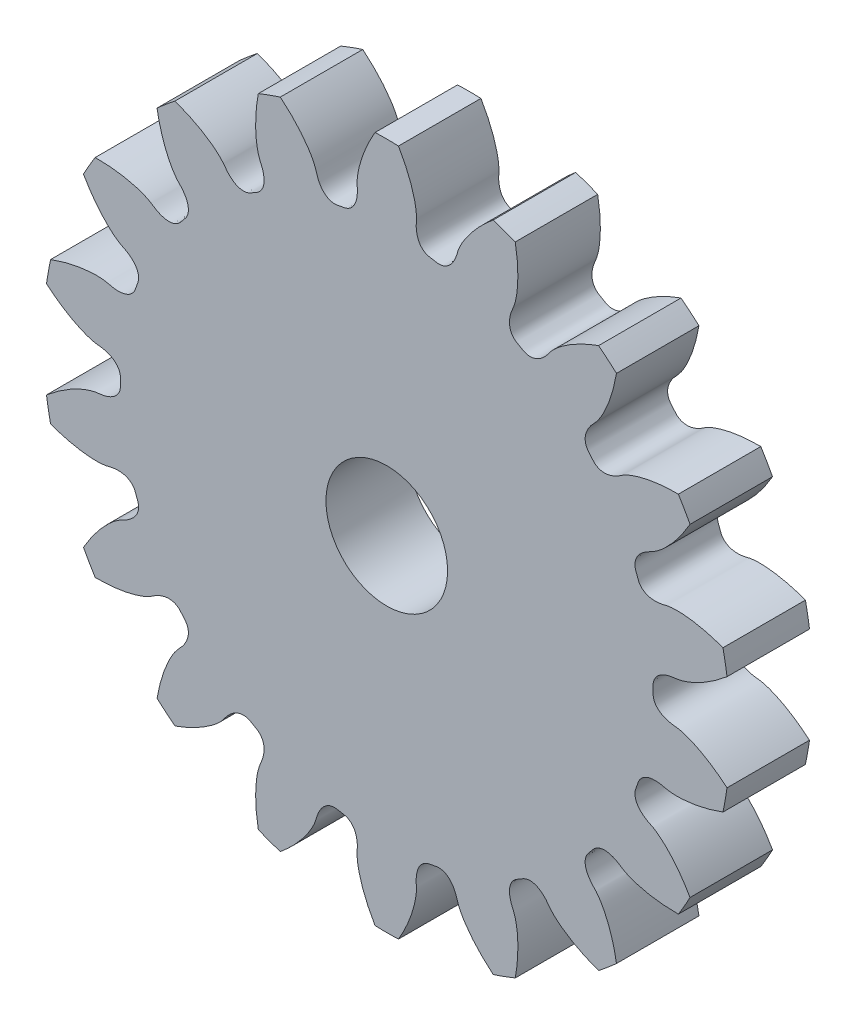
SolidWorks part; units mm, degrees
ref_plane "Front Plane" through (0, 0, 0) normal (0, 0, 1) x (1, 0, 0)
ref_plane "Top Plane" through (0, 0, 0) normal (0, 1, 0) x (1, 0, 0)
ref_plane "Right Plane" through (0, 0, 0) normal (1, 0, 0) x (0, 0, -1)
ref_axis "Axis1" through (0, 0, 55) along (0, 0, -1)
sketch "SketchRevolveSpurGear1" plane through (0, 0, 0) normal (1, 0, 0) x (0, 0, -1)
  line L0 (0, 0) -> (1, 0) construction
  line L1 (-2, 0) -> (-2, 16.6667)
  line L2 (-2, 16.6667) -> (2, 16.6667)
  line L3 (2, 16.6667) -> (2, 0)
  line L4 (2, 0) -> (-2, 0)
  dimension "Side1" = 2
  dimension "OutsideRadius" = 16.6667
  dimension "Side2" = 2
revolve "SpurGear1" add sketch "SketchRevolveSpurGear1" angle 360 about L0 other way angle 360
sketch "SketchToothSpurGear1" plane through (0, 0, 0) normal (0, 0, 1) x (1, 0, 0)
  arc A0 (16.5775, 2.3974) -> (16.5775, -2.3974) centre (0, 0) cw
  spline S0 degree 3 poles (16.5775, -2.3974) (16.3745, -2.2215) (16.101, -2.0047) (15.752, -1.7646) (15.5625, -1.643) (15.3817, -1.5351) (15.2102, -1.44) (15.0487, -1.3571) (14.8977, -1.2856) (14.7578, -1.2248) (14.6296, -1.1738) (14.5135, -1.1319) (14.4099, -1.0983) (14.3192, -1.072) (14.2418, -1.0522) (14.178, -1.038) (14.128, -1.0286) (14.0922, -1.023) (14.0706, -1.0202) (13.9852, -1.0124) (13.8776, -1.0014) (13.7458, -0.9761) (13.6619, -0.9562) (13.5812, -0.9329) (13.5035, -0.906) (13.4285, -0.875) (13.3561, -0.8396) (13.286, -0.799) (13.2182, -0.7521) (13.1528, -0.6977) (13.0904, -0.634) (13.0327, -0.5594) (12.9821, -0.4722) (12.9425, -0.3724) (12.9212, -0.2705) (12.9123, -0.1452) (12.9195, 0) (12.9123, 0.1452) (12.9212, 0.2705) (12.9425, 0.3724) (12.9821, 0.4722) (13.0327, 0.5594) (13.0904, 0.634) (13.1528, 0.6977) (13.2182, 0.7521) (13.286, 0.799) (13.3561, 0.8396) (13.4285, 0.875) (13.5035, 0.906) (13.5812, 0.9329) (13.6619, 0.9562) (13.7458, 0.9761) (13.8776, 1.0014) (13.9852, 1.0124) (14.0706, 1.0202) (14.0922, 1.023) (14.128, 1.0286) (14.178, 1.038) (14.2418, 1.0522) (14.3192, 1.072) (14.4099, 1.0983) (14.5135, 1.1319) (14.6296, 1.1738) (14.7578, 1.2248) (14.8977, 1.2856) (15.0487, 1.3571) (15.2102, 1.44) (15.3817, 1.5351) (15.5625, 1.643) (15.752, 1.7646) (16.101, 2.0047) (16.3745, 2.2215) (16.5775, 2.3974) knots 0 0 0 0 0.086714 0.112496 0.136716 0.159373 0.180468 0.2 0.217969 0.234376 0.24922 0.262502 0.274221 0.284378 0.292972 0.300003 0.305472 0.309379 0.311722 0.312504 0.337039 0.346571 0.355827 0.364844 0.373672 0.382369 0.391008 0.399681 0.408498 0.41759 0.427106 0.437197 0.447986 0.459523 0.471726 0.481412 0.5 0.518588 0.528274 0.540477 0.552014 0.562803 0.572894 0.58241 0.591502 0.600319 0.608992 0.617631 0.626328 0.635156 0.644173 0.653429 0.662961 0.687496 0.688278 0.690621 0.694528 0.699997 0.707028 0.715622 0.725779 0.737498 0.75078 0.765624 0.782031 0.8 0.819532 0.840627 0.863284 0.887504 0.913286 1 1 1 1
extrude "ToothExtrudeCutSpurGear1" cut sketch "SketchToothSpurGear1" against normal blind 9.525 and the other way blind 9.525
pattern_circular "PatternSpurGear1" count 18 over 360 about axis through (0, 0, 55) along (0, 0, -1) of "ToothExtrudeCutSpurGear1"
sketch "BoreRevolveSketch" plane through (0, 0, 0) normal (1, 0, 0) x (0, 0, -1)
  line L0 (0, 0) -> (1, 0) construction
  line L1 (-9.525, 0) -> (9.525, 0)
  line L2 (9.525, 0) -> (9.525, 2.95)
  line L3 (9.525, 2.95) -> (-9.525, 2.95)
  line L4 (-9.525, 2.95) -> (-9.525, 0)
  dimension "BoreSide1" = 9.525
  dimension "TaperSide1" = 2.95
  dimension "BoreSide2" = 9.525
  dimension "TaperSide2" = 2.95
revolve "BoreRevolveCut" cut sketch "BoreRevolveSketch" angle 360 about L0
sketch "AuxiliarySketchSpurGear1" plane through (0, 0, 0) normal (0, 0, 1) x (1, 0, 0)
  circle A0 centre (0, 0) radius 15 construction
  circle A1 centre (0, 0) radius 14.0954 construction
  circle A2 centre (0, 0) radius 14.0954 construction
  circle A3 centre (0, 0) radius 16.6667 construction
  circle A4 centre (0, 0) radius 12.9167 construction
  dimension "PitchDiameter" = 30
  dimension "BaseDiameter" = 28.1908
  dimension "FormDiameter" = 28.1908
  dimension "MajorDiameter" = 33.3333
  dimension "MinorDiameter" = 25.8333
